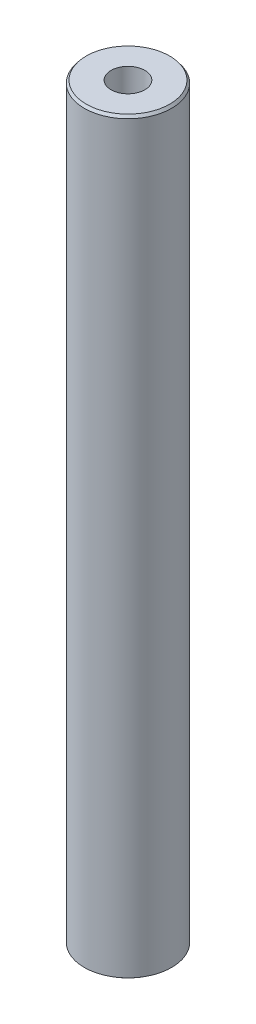
SolidWorks part; units mm, degrees
ref_plane "Front Plane" through (0, 0, 0) normal (0, 0, 1) x (1, 0, 0)
ref_plane "Top Plane" through (0, 0, 0) normal (0, 1, 0) x (1, 0, 0)
ref_plane "Right Plane" through (0, 0, 0) normal (1, 0, 0) x (0, 0, -1)
sketch "Sketch1" plane through (0, 0, 0) normal (0, 1, 0) x (1, 0, 0)
  circle A0 centre (0, 0) radius 35
  dimension "SHAFT_OD" = 70
extrude "Boss-Extrude1" add sketch "Sketch1" along normal blind 600
sketch "Sketch2" plane through (0, 0, 0) normal (0, 1, 0) x (1, 0, 0)
  circle A0 centre (0, 0) radius 13.5304
  dimension "BORE_D" = 27.0608
extrude "Cut-Extrude1" cut sketch "Sketch2" along normal through all
chamfer "Chamfer1" distance 2.1159 angle 36.238 2 edges at (0, 600, 35) (0, 0, 35) first distance on face at (0, 600, 35) first distance on face at (0, 0, 13.5304)
